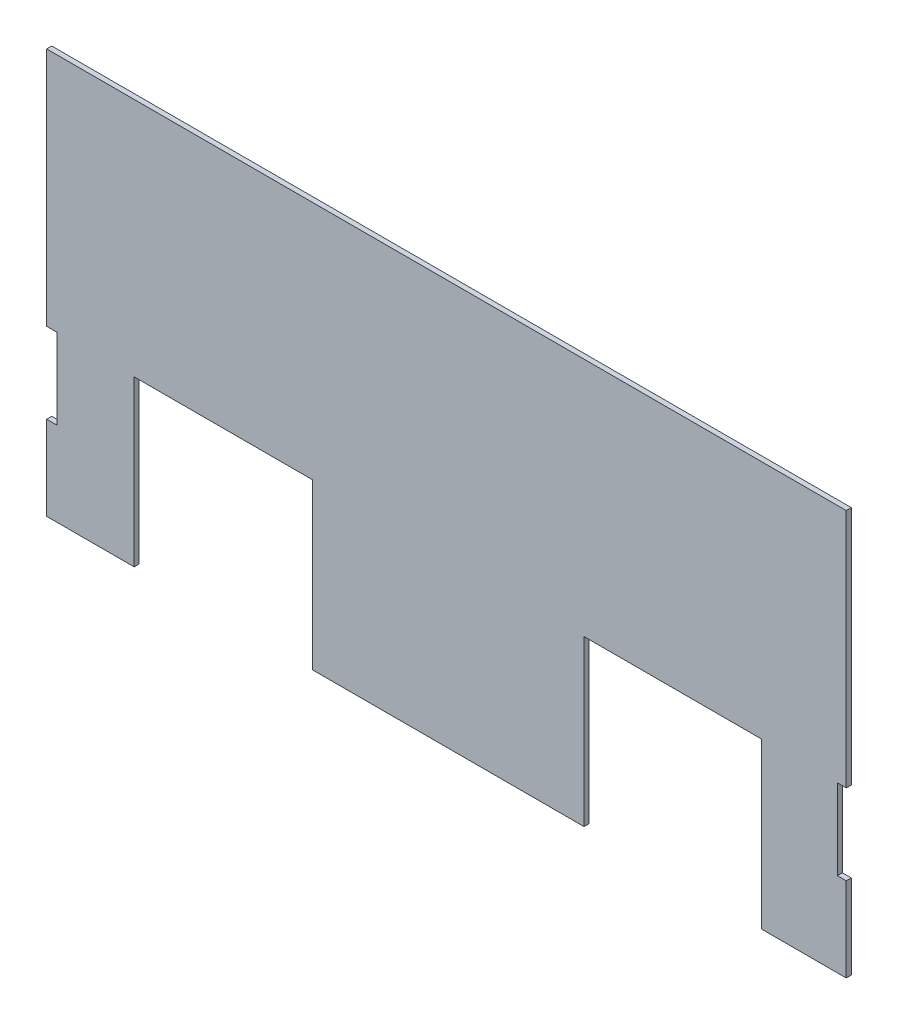
SolidWorks part; units mm, degrees
material "Polypropylene"
ref_plane "Front Plane" through (0, 0, 0) normal (0, 0, 1) x (1, 0, 0)
ref_plane "Top Plane" through (0, 0, 0) normal (0, 1, 0) x (1, 0, 0)
ref_plane "Right Plane" through (0, 0, 0) normal (1, 0, 0) x (0, 0, -1)
sketch "Sketch1" plane through (0, 0, 0) normal (0, 0, 1) x (1, 0, 0)
  line L1 (0, 0) -> (752.475, 0)
  line L2 (0, 0) -> (0, -381)
  line L3 (0, -381) -> (752.475, -381)
  line L4 (752.475, 0) -> (752.475, -381)
  dimension "D1" = 381
  dimension "D2" = 752.475
extrude "Boss-Extrude1" add sketch "Sketch1" along normal blind 4.7625
sketch "Sketch2" plane through (0, 0, 0) normal (0, 0, -1) x (-1, 0, 0)
  line L0 (-752.475, -381) -> (-752.475, 0) construction
  line L1 (-752.475, -301.8032) -> (-744.0955, -301.8032)
  line L2 (-752.475, -301.8032) -> (-752.475, -226.1009)
  line L3 (-752.475, -226.1009) -> (-744.0955, -226.1009)
  line L4 (-744.0955, -301.8032) -> (-744.0955, -226.1009)
  line L5 (-747.0902, -226.1009) -> (-741.9848, -226.1009) construction
extrude "Cut-Extrude1" cut sketch "Sketch2" against normal blind 10.668
sketch "Sketch3" plane through (0, 0, 0) normal (0, 0, -1) x (-1, 0, 0)
  line L0 (-744.0955, -301.8032) -> (4.7625, -299.8134) construction
  line L1 (0, 0) -> (0, -381) construction
  line L2 (0, -301.8032) -> (-9.6827, -301.8032)
  line L3 (0, -301.8032) -> (0, -226.0952)
  line L4 (0, -226.0952) -> (-9.6827, -226.0952)
  line L5 (-9.6827, -301.8032) -> (-9.6827, -226.0952)
extrude "Cut-Extrude2" cut sketch "Sketch3" against normal blind 10.668
sketch "Sketch4" plane through (0, 0, 0) normal (0, 0, -1) x (-1, 0, 0)
  line L0 (-439.7375, -226.1009) -> (-731.8375, -226.1009) construction
  line L1 (-672.6207, -226.1009) -> (-505.7165, -226.1009)
  line L2 (-672.6207, -226.1009) -> (-672.6207, -381)
  line L3 (-672.6207, -381) -> (-505.7165, -381)
  line L4 (-505.7165, -226.1009) -> (-505.7165, -381)
  line L5 (0, -381) -> (-752.475, -381) construction
extrude "Cut-Extrude3" cut sketch "Sketch4" against normal blind 10.668
sketch "Sketch5" plane through (0, 0, 0) normal (0, 0, -1) x (-1, 0, 0)
  line L6 (0, -381) -> (-505.7165, -381) construction
  line L7 (-82.3145, -381) -> (-249.9649, -381)
  line L8 (-82.3145, -381) -> (-82.3145, -226.1009)
  line L9 (-82.3145, -226.1009) -> (-249.9649, -226.1009)
  line L10 (-249.9649, -381) -> (-249.9649, -226.1009)
  line L11 (-20.6375, -226.1009) -> (-312.7375, -226.1009) construction
extrude "Cut-Extrude5" cut sketch "Sketch5" against normal blind 10.668
